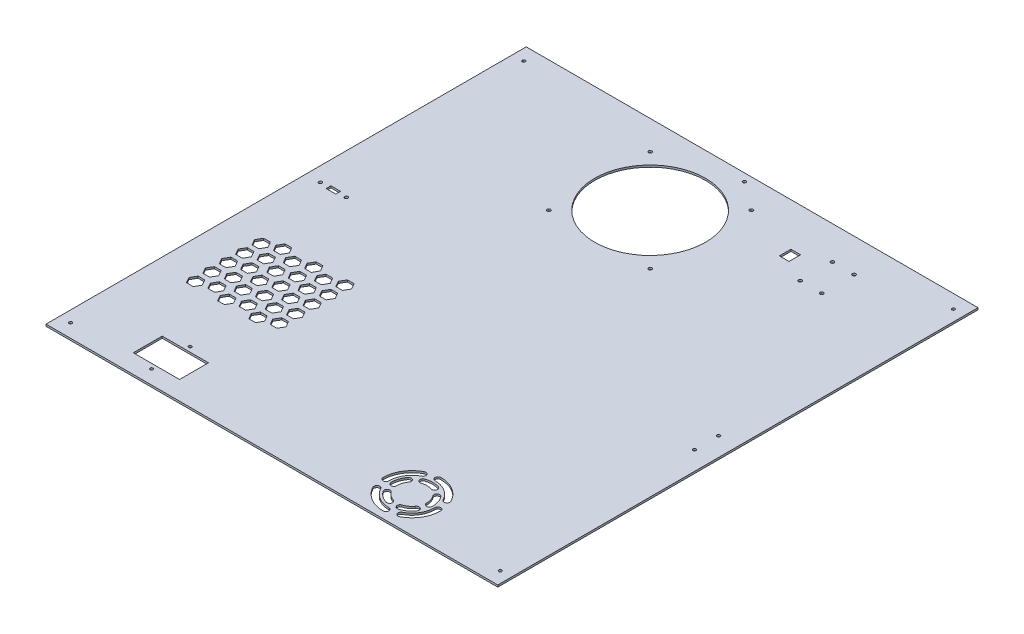
SolidWorks part; units mm, degrees
ref_plane "Alzado" through (0, 0, 0) normal (0, 0, 1) x (1, 0, 0)
ref_plane "Planta" through (0, 0, 0) normal (0, 1, 0) x (1, 0, 0)
ref_plane "Vista lateral" through (0, 0, 0) normal (1, 0, 0) x (0, 0, -1)
sketch "Croquis1" plane through (0, 0, 0) normal (0, 1, 0) x (1, 0, 0)
  line L1 (0, 0) -> (470.5, 0)
  line L2 (0, 0) -> (0, 420)
  line L3 (0, 420) -> (470.5, 420)
  line L4 (470.5, 0) -> (470.5, 420)
  dimension "D1" = 420
  dimension "D2" = 470.5
extrude "Saliente-Extruir1" add sketch "Croquis1" along normal blind 2
sketch "Croquis2" plane through (0, 2, 0) normal (0, 1, 0) x (1, 0, 0)
  line L0 (470.5, 420) -> (0, 420) construction
  line L1 (0, 420) -> (0, 0) construction
  line L2 (235.25, 420) -> (235.25, 0) construction
  line L3 (0, 0) -> (470.5, 0) construction
  line L4 (0, 210) -> (470.5, 210) construction
  line L5 (470.5, 0) -> (470.5, 420) construction
  circle A0 centre (12.5, 405) radius 1.55
  circle A1 centre (458, 405) radius 1.55
  circle A2 centre (458, 15) radius 1.55
  circle A3 centre (12.5, 15) radius 1.55
  dimension "D1" = 3.1
  dimension "D2" = 15
  dimension "D3" = 12.5
extrude "Cortar-Extruir1" cut sketch "Croquis2" against normal up to surface (2 mm away) up to face at (235.25, 0, -210)
sketch "Croquis3" plane through (0, 2, 0) normal (0, 1, 0) x (1, 0, 0)
  line L0 (470, 419.5) -> (0.5, 419.5)
  line L1 (0.5, 419.5) -> (0.5, 0.5)
  line L2 (0.5, 0.5) -> (470, 0.5)
  line L3 (470, 0.5) -> (470, 419.5)
  line L4 (0, 420) -> (0, 0)
  line L5 (0, 0) -> (470.5, 0)
  line L6 (470.5, 0) -> (470.5, 420)
  line L7 (470.5, 420) -> (0, 420)
  line L8 (0, 420) -> (0, 0)
  line L9 (0, 0) -> (470.5, 0)
  line L10 (470.5, 0) -> (470.5, 420)
  line L11 (470.5, 420) -> (0, 420)
  dimension "D1" = 0
  dimension "D2" = 0.5
extrude "Cortar-Extruir2" cut sketch "Croquis3" against normal up to surface (2 mm away) up to face at (12.5, 0, -16.55)
sketch "Croquis4" plane through (0, 2, 0) normal (0, 1, 0) x (1, 0, 0)
  line L0 (0.5, 0.5) -> (470, 0.5) construction
  line L1 (0.5, 419.5) -> (0.5, 0.5) construction
  circle A0 centre (343.5, 38) radius 27 construction
  arc A1 (343.5, 65) -> (367.4419, 50.4815) centre (343.5, 38) cw construction
  arc A2 (370.1021, 51.8683) -> (343.5, 68) centre (343.5, 38) ccw
  arc A3 (364.7817, 49.0947) -> (343.5, 62) centre (343.5, 38) ccw
  arc A4 (364.7817, 49.0947) -> (370.1021, 51.8683) centre (367.4419, 50.4815) ccw
  arc A5 (343.5, 68) -> (343.5, 62) centre (343.5, 65) ccw
  arc A6 (354.5947, 16.7183) -> (367.5, 38) centre (343.5, 38) ccw
  arc A7 (354.5947, 16.7183) -> (357.3683, 11.3979) centre (355.9815, 14.0581) ccw
  arc A8 (373.5, 38) -> (367.5, 38) centre (370.5, 38) ccw
  arc A9 (357.3683, 11.3979) -> (373.5, 38) centre (343.5, 38) ccw
  arc A10 (370.5, 38) -> (355.9815, 14.0581) centre (343.5, 38) cw construction
  arc A11 (322.2183, 26.9053) -> (343.5, 14) centre (343.5, 38) ccw
  arc A12 (322.2183, 26.9053) -> (316.8979, 24.1317) centre (319.5581, 25.5185) ccw
  arc A13 (343.5, 8) -> (343.5, 14) centre (343.5, 11) ccw
  arc A14 (316.8979, 24.1317) -> (343.5, 8) centre (343.5, 38) ccw
  arc A15 (343.5, 11) -> (319.5581, 25.5185) centre (343.5, 38) cw construction
  arc A16 (332.4053, 59.2817) -> (319.5, 38) centre (343.5, 38) ccw
  arc A17 (332.4053, 59.2817) -> (329.6317, 64.6021) centre (331.0185, 61.9419) ccw
  arc A18 (313.5, 38) -> (319.5, 38) centre (316.5, 38) ccw
  arc A19 (329.6317, 64.6021) -> (313.5, 38) centre (343.5, 38) ccw
  arc A20 (316.5, 38) -> (331.0185, 61.9419) centre (343.5, 38) cw construction
  circle A21 centre (343.5, 38) radius 18.5 construction
  arc A22 (337.5, 55.5) -> (349.5, 55.5) centre (343.5, 38) cw construction
  arc A23 (350.473, 58.3378) -> (336.527, 58.3378) centre (343.5, 38) ccw
  arc A24 (348.527, 52.6622) -> (338.473, 52.6622) centre (343.5, 38) ccw
  arc A25 (348.527, 52.6622) -> (350.473, 58.3378) centre (349.5, 55.5) ccw
  arc A26 (336.527, 58.3378) -> (338.473, 52.6622) centre (337.5, 55.5) ccw
  arc A27 (358.2894, 49.1141) -> (361.9976, 37.7015) centre (343.5, 38) cw construction
  arc A28 (364.9972, 37.653) -> (360.6877, 50.9164) centre (343.5, 38) ccw
  arc A29 (358.998, 37.7499) -> (355.8911, 47.3118) centre (343.5, 38) ccw
  arc A30 (358.998, 37.7499) -> (364.9972, 37.653) centre (361.9976, 37.7015) ccw
  arc A31 (360.6877, 50.9164) -> (355.8911, 47.3118) centre (358.2894, 49.1141) ccw
  arc A32 (358.6403, 27.3689) -> (348.9321, 20.3155) centre (343.5, 38) cw construction
  arc A33 (349.813, 17.4477) -> (361.0955, 25.645) centre (343.5, 38) ccw
  arc A34 (348.0513, 23.1832) -> (356.1852, 29.0929) centre (343.5, 38) ccw
  arc A35 (348.0513, 23.1832) -> (349.813, 17.4477) centre (348.9321, 20.3155) ccw
  arc A36 (361.0955, 25.645) -> (356.1852, 29.0929) centre (358.6403, 27.3689) ccw
  arc A37 (338.0679, 20.3155) -> (328.3597, 27.3689) centre (343.5, 38) cw construction
  arc A38 (325.9045, 25.645) -> (337.187, 17.4477) centre (343.5, 38) ccw
  arc A39 (330.8148, 29.0929) -> (338.9487, 23.1832) centre (343.5, 38) ccw
  arc A40 (330.8148, 29.0929) -> (325.9045, 25.645) centre (328.3597, 27.3689) ccw
  arc A41 (337.187, 17.4477) -> (338.9487, 23.1832) centre (338.0679, 20.3155) ccw
  arc A42 (325.0024, 37.7015) -> (328.7106, 49.1141) centre (343.5, 38) cw construction
  arc A43 (326.3123, 50.9164) -> (322.0028, 37.653) centre (343.5, 38) ccw
  arc A44 (331.1089, 47.3118) -> (328.002, 37.7499) centre (343.5, 38) ccw
  arc A45 (331.1089, 47.3118) -> (326.3123, 50.9164) centre (328.7106, 49.1141) ccw
  arc A46 (322.0028, 37.653) -> (328.002, 37.7499) centre (325.0024, 37.7015) ccw
  circle A94 centre (458, 405) radius 1.55 construction
  point P9 (357.5, 61.0868)
  point P19 (366.5868, 24)
  point P26 (329.5, 14.9132)
  point P33 (320.4132, 52)
  point P38 (343.5, 38)
  point P40 (343.5, 56.5)
  point P48 (361.0945, 43.7168)
  point P57 (354.374, 23.0332)
  point P64 (332.626, 23.0332)
  point P71 (325.9055, 43.7168)
  point P76 (343.5, 38)
  point P125 (302, 221.5)
  point P183 (302, 221.5)
  dimension "D1" = 54
  dimension "D7" = 37
  dimension "D2" = 37.5
  dimension "D3" = 343
  dimension "D4" = 28
  dimension "D5" = 6
  dimension "D8" = 12
  dimension "D9" = 6
  dimension "D6" = 4
  dimension "D10" = 5
extrude "Cortar-Extruir3" cut sketch "Croquis4" against normal up to surface (2 mm away) up to face at (12.5, 0, -406.55)
sketch "Croquis5" plane through (0, 0, 0) normal (0, -1, 0) x (1, 0, 0)
  line L0 (120, -35.5) -> (72, -35.5) construction
  line L1 (120, -50.5) -> (72, -50.5)
  line L2 (120, -50.5) -> (120, -20.5)
  line L3 (120, -20.5) -> (72, -20.5)
  line L4 (72, -50.5) -> (72, -20.5)
  line L5 (470, -0.5) -> (470, -419.5) construction
  line L6 (0.5, -0.5) -> (470, -0.5) construction
  circle A1 centre (96, -15.5) radius 1.55
  circle A2 centre (96, -55.5) radius 1.55
  dimension "D3" = 3.1
  dimension "D1" = 48
  dimension "D2" = 30
  dimension "D4" = 5
  dimension "D5" = 24
  dimension "D6" = 350
  dimension "D7" = 20
extrude "Cortar-Extruir4" cut sketch "Croquis5" against normal up to surface (2 mm away) up to face at (343.5, 2, -55.5135)
sketch "Croquis8" plane through (0, 0, 0) normal (0, -1, 0) x (1, 0, 0)
  line L1 (470, -419.5) -> (0.5, -419.5)
  line L2 (470, -419.5) -> (470, -449.5)
  line L3 (470, -449.5) -> (0.5, -449.5)
  line L4 (0.5, -419.5) -> (0.5, -449.5)
  dimension "D1" = 30
extrude "Saliente-Extruir2" add sketch "Croquis8" against normal up to surface (2 mm away) up to face at (96, 2, -57.05)
sketch "Croquis10" plane through (0, 0, 0) normal (0, -1, 0) x (1, 0, 0)
  circle A0 centre (458, -405) radius 1.75
  circle A1 centre (12.5, -405) radius 1.75
  dimension "D1" = 3.5
  dimension "D2" = 3.5
extrude "Saliente-Extruir3" add sketch "Croquis10" against normal up to surface (2 mm away) up to face at (96, 2, -57.05)
sketch "Croquis11" plane through (0, 0, -449.5) normal (0, 0, -1) x (-1, 0, 0)
  line L4 (-0.5, 2) -> (-470, 2)
  line L5 (-470, 2) -> (-470, 0)
  line L6 (-470, 0) -> (-0.5, 0)
  line L7 (-0.5, 0) -> (-0.5, 2)
  line L8 (-0.5, 2) -> (-470, 2)
  line L9 (-470, 2) -> (-470, 0)
  line L10 (-470, 0) -> (-0.5, 0)
  line L11 (-0.5, 0) -> (-0.5, 2)
  dimension "D1" = 0
extrude "Saliente-Extruir4" add sketch "Croquis11" along normal blind 50
sketch "Croquis12" plane through (0, 0, 0) normal (0, -1, 0) x (1, 0, 0)
  line L0 (470, -0.5) -> (470, -499.5) construction
  line L1 (0.5, -499.5) -> (0.5, -0.5) construction
  line L3 (470, -499.5) -> (0.5, -499.5) construction
  circle A0 centre (458, -485) radius 1.55
  circle A1 centre (12.5, -485) radius 1.55
  dimension "D1" = 3.1
  dimension "D2" = 3.1
  dimension "D3" = 12
  dimension "D4" = 12
  dimension "D5" = 14.5
  dimension "D6" = 14.5
extrude "Cortar-Extruir8" cut sketch "Croquis12" against normal up to surface (2 mm away) up to face at (96, 2, -57.05)
sketch "Croquis13" plane through (0, 0, 0) normal (0, -1, 0) x (1, 0, 0)
  line L0 (470, -0.5) -> (470, -499.5) construction
  line L1 (470, -499.5) -> (0.5, -499.5) construction
  line L3 (330, -454.5) -> (320, -454.5)
  line L4 (330, -454.5) -> (330, -442.5)
  line L5 (330, -442.5) -> (320, -442.5)
  line L6 (320, -454.5) -> (320, -442.5)
  circle A0 centre (353, -464.5) radius 1.75
  circle A1 centre (353, -431) radius 1.75
  circle A2 centre (375.5, -464.5) radius 1.75
  circle A3 centre (375.5, -431) radius 1.75
  point P16 (0, 0)
  point P17 (0, 0)
  dimension "D1" = 3.5
  dimension "D2" = 33.5
  dimension "D3" = 117
  dimension "D4" = 35
  dimension "D5" = 10
  dimension "D6" = 12
  dimension "D7" = 45
  dimension "D8" = 150
  dimension "D9" = 22.5
  dimension "D10" = 22.5
extrude "Cortar-Extruir9" cut sketch "Croquis13" against normal up to surface (2 mm away) up to face at (458, 2, -486.55)
sketch "Croquis15" plane through (0, 0, 0) normal (0, -1, 0) x (1, 0, 0)
  line L0 (470, -0.5) -> (470, -499.5) construction
  line L2 (470, -499.5) -> (0.5, -499.5) construction
  circle A0 centre (450, -249.5) radius 1.6
  circle A1 centre (450, -224.5) radius 1.6
  dimension "D1" = 3.2
  dimension "D2" = 25
  dimension "D3" = 20
  dimension "D4" = 250
extrude "Cortar-Extruir11" cut sketch "Croquis15" against normal up to surface (2 mm away) up to face at (353, 2, -432.75)
sketch "Croquis16" plane through (0, 0, 0) normal (0, -1, 0) x (1, 0, 0)
  line L4 (0.5, -0.5) -> (470, -0.5) construction
  line L5 (0.5, -499.5) -> (0.5, -0.5) construction
  line L6 (470, -0.5) -> (470, -499.5) construction
  line L7 (470, -499.5) -> (0.5, -499.5) construction
  line L8 (1, -1) -> (1, -499)
  line L9 (1, -499) -> (469.5, -499)
  line L10 (469.5, -499) -> (469.5, -1)
  line L11 (469.5, -1) -> (1, -1)
  line L12 (1, -1) -> (1, -499)
  line L13 (1, -499) -> (469.5, -499)
  line L14 (469.5, -499) -> (469.5, -1)
  line L15 (469.5, -1) -> (1, -1)
  line L16 (0.5, -0.5) -> (470, -0.5)
  line L17 (0.5, -499.5) -> (0.5, -0.5)
  line L18 (470, -0.5) -> (470, -499.5)
  line L19 (470, -499.5) -> (0.5, -499.5)
  dimension "D1" = 0.5
extrude "Cortar-Extruir12" cut sketch "Croquis16" against normal up to surface (2 mm away) up to face at (450, 2, -251.1)
sketch "Croquis17" plane through (0, 2, 0) normal (0, 1, 0) x (1, 0, 0)
  line L0 (469.5, 499) -> (1, 499) construction
  line L1 (1, 499) -> (1, 1) construction
  circle A0 centre (235.25, 491) radius 1.6
  dimension "D1" = 3.2
  dimension "D2" = 8
  dimension "D3" = 234.25
extrude "Cortar-Extruir13" cut sketch "Croquis17" against normal up to surface (2 mm away) up to face at (12.5, 0, -16.55)
sketch "Croquis18" plane through (0, 0, 0) normal (0, -1, 0) x (1, 0, 0)
  line L0 (34.5, -270.5) -> (16, -270.5) construction
  line L1 (34.5, -273) -> (24.5, -273)
  line L2 (34.5, -273) -> (34.5, -268)
  line L3 (34.5, -268) -> (24.5, -268)
  line L4 (24.5, -273) -> (24.5, -268)
  line L5 (34.5, -270.5) -> (43, -270.5) construction
  line L6 (29.5, -273) -> (29.5, -268) construction
  line L7 (1, -1) -> (1, -499) construction
  line L9 (72, -50.5) -> (120, -50.5) construction
  circle A0 centre (16, -270.5) radius 1.65
  circle A1 centre (43, -270.5) radius 1.65
  dimension "D3" = 3.3
  dimension "D4" = 3.3
  dimension "D1" = 10
  dimension "D2" = 5
  dimension "D5" = 27
  dimension "D6" = 13.5
  dimension "D7" = 15
  dimension "D8" = 220
extrude "Cortar-Extruir14" cut sketch "Croquis18" against normal up to surface (2 mm away) up to face at (235.25, 2, -489.4)
sketch "Croquis19" plane through (0, 0, 0) normal (0, -1, 0) x (1, 0, 0)
  line L0 (1, -1) -> (1, -499) construction
  line L1 (114.0718, -191) -> (117.5359, -197)
  line L2 (117.5359, -197) -> (124.4641, -197)
  line L3 (124.4641, -197) -> (127.9282, -191)
  line L4 (127.9282, -191) -> (124.4641, -185)
  line L5 (124.4641, -185) -> (117.5359, -185)
  line L6 (117.5359, -185) -> (114.0718, -191)
  line L7 (469.5, -1) -> (1, -1) construction
  line L176 (114.0718, -174) -> (117.5359, -180)
  line L177 (97.906, -185) -> (101.3701, -191)
  line L178 (101.3701, -191) -> (108.2983, -191)
  line L179 (108.2983, -191) -> (111.7624, -185)
  line L180 (111.7624, -185) -> (108.2983, -179)
  line L181 (108.2983, -179) -> (101.3701, -179)
  line L182 (101.3701, -179) -> (97.906, -185)
  line L183 (117.5359, -180) -> (124.4641, -180)
  line L184 (124.4641, -180) -> (127.9282, -174)
  line L185 (127.9282, -174) -> (124.4641, -168)
  line L186 (124.4641, -168) -> (117.5359, -168)
  line L187 (117.5359, -168) -> (114.0718, -174)
  line L188 (97.906, -168) -> (101.3701, -174)
  line L189 (101.3701, -174) -> (108.2983, -174)
  line L190 (108.2983, -174) -> (111.7624, -168)
  line L191 (111.7624, -168) -> (108.2983, -162)
  line L192 (108.2983, -162) -> (101.3701, -162)
  line L193 (101.3701, -162) -> (97.906, -168)
  line L194 (114.0718, -157) -> (117.5359, -163)
  line L195 (117.5359, -163) -> (124.4641, -163)
  line L196 (124.4641, -163) -> (127.9282, -157)
  line L197 (127.9282, -157) -> (124.4641, -151)
  line L198 (124.4641, -151) -> (117.5359, -151)
  line L199 (117.5359, -151) -> (114.0718, -157)
  line L200 (97.906, -151) -> (101.3701, -157)
  line L201 (101.3701, -157) -> (108.2983, -157)
  line L202 (108.2983, -157) -> (111.7624, -151)
  line L203 (111.7624, -151) -> (108.2983, -145)
  line L204 (108.2983, -145) -> (101.3701, -145)
  line L205 (101.3701, -145) -> (97.906, -151)
  line L206 (114.0718, -140) -> (117.5359, -146)
  line L207 (117.5359, -146) -> (124.4641, -146)
  line L208 (124.4641, -146) -> (127.9282, -140)
  line L209 (127.9282, -140) -> (124.4641, -134)
  line L210 (124.4641, -134) -> (117.5359, -134)
  line L211 (117.5359, -134) -> (114.0718, -140)
  line L212 (97.906, -134) -> (101.3701, -140)
  line L213 (101.3701, -140) -> (108.2983, -140)
  line L214 (108.2983, -140) -> (111.7624, -134)
  line L215 (111.7624, -134) -> (108.2983, -128)
  line L216 (108.2983, -128) -> (101.3701, -128)
  line L217 (101.3701, -128) -> (97.906, -134)
  line L218 (114.0718, -123) -> (117.5359, -129)
  line L219 (117.5359, -129) -> (124.4641, -129)
  line L220 (124.4641, -129) -> (127.9282, -123)
  line L221 (127.9282, -123) -> (124.4641, -117)
  line L222 (124.4641, -117) -> (117.5359, -117)
  line L223 (117.5359, -117) -> (114.0718, -123)
  line L224 (97.906, -117) -> (101.3701, -123)
  line L225 (101.3701, -123) -> (108.2983, -123)
  line L226 (108.2983, -123) -> (111.7624, -117)
  line L227 (111.7624, -117) -> (108.2983, -111)
  line L228 (108.2983, -111) -> (101.3701, -111)
  line L229 (101.3701, -111) -> (97.906, -117)
  line L230 (81.7402, -191) -> (85.2043, -197)
  line L231 (85.2043, -197) -> (92.1325, -197)
  line L232 (92.1325, -197) -> (95.5966, -191)
  line L233 (95.5966, -191) -> (92.1325, -185)
  line L234 (92.1325, -185) -> (85.2043, -185)
  line L235 (85.2043, -185) -> (81.7402, -191)
  line L236 (81.7402, -174) -> (85.2043, -180)
  line L237 (65.5744, -185) -> (69.0385, -191)
  line L238 (69.0385, -191) -> (75.9667, -191)
  line L239 (75.9667, -191) -> (79.4308, -185)
  line L240 (79.4308, -185) -> (75.9667, -179)
  line L241 (75.9667, -179) -> (69.0385, -179)
  line L242 (69.0385, -179) -> (65.5744, -185)
  line L243 (85.2043, -180) -> (92.1325, -180)
  line L244 (92.1325, -180) -> (95.5966, -174)
  line L245 (95.5966, -174) -> (92.1325, -168)
  line L246 (92.1325, -168) -> (85.2043, -168)
  line L247 (85.2043, -168) -> (81.7402, -174)
  line L248 (65.5744, -168) -> (69.0385, -174)
  line L249 (69.0385, -174) -> (75.9667, -174)
  line L250 (75.9667, -174) -> (79.4308, -168)
  line L251 (79.4308, -168) -> (75.9667, -162)
  line L252 (75.9667, -162) -> (69.0385, -162)
  line L253 (69.0385, -162) -> (65.5744, -168)
  line L254 (81.7402, -157) -> (85.2043, -163)
  line L255 (85.2043, -163) -> (92.1325, -163)
  line L256 (92.1325, -163) -> (95.5966, -157)
  line L257 (95.5966, -157) -> (92.1325, -151)
  line L258 (92.1325, -151) -> (85.2043, -151)
  line L259 (85.2043, -151) -> (81.7402, -157)
  line L260 (65.5744, -151) -> (69.0385, -157)
  line L261 (69.0385, -157) -> (75.9667, -157)
  line L262 (75.9667, -157) -> (79.4308, -151)
  line L263 (79.4308, -151) -> (75.9667, -145)
  line L264 (75.9667, -145) -> (69.0385, -145)
  line L265 (69.0385, -145) -> (65.5744, -151)
  line L266 (81.7402, -140) -> (85.2043, -146)
  line L267 (85.2043, -146) -> (92.1325, -146)
  line L268 (92.1325, -146) -> (95.5966, -140)
  line L269 (95.5966, -140) -> (92.1325, -134)
  line L270 (92.1325, -134) -> (85.2043, -134)
  line L271 (85.2043, -134) -> (81.7402, -140)
  line L272 (65.5744, -134) -> (69.0385, -140)
  line L273 (69.0385, -140) -> (75.9667, -140)
  line L274 (75.9667, -140) -> (79.4308, -134)
  line L275 (79.4308, -134) -> (75.9667, -128)
  line L276 (75.9667, -128) -> (69.0385, -128)
  line L277 (69.0385, -128) -> (65.5744, -134)
  line L278 (81.7402, -123) -> (85.2043, -129)
  line L279 (85.2043, -129) -> (92.1325, -129)
  line L280 (92.1325, -129) -> (95.5966, -123)
  line L281 (95.5966, -123) -> (92.1325, -117)
  line L282 (92.1325, -117) -> (85.2043, -117)
  line L283 (85.2043, -117) -> (81.7402, -123)
  line L284 (65.5744, -117) -> (69.0385, -123)
  line L285 (69.0385, -123) -> (75.9667, -123)
  line L286 (75.9667, -123) -> (79.4308, -117)
  line L287 (79.4308, -117) -> (75.9667, -111)
  line L288 (75.9667, -111) -> (69.0385, -111)
  line L289 (69.0385, -111) -> (65.5744, -117)
  line L290 (49.4086, -191) -> (52.8727, -197)
  line L291 (52.8727, -197) -> (59.8009, -197)
  line L292 (59.8009, -197) -> (63.265, -191)
  line L293 (63.265, -191) -> (59.8009, -185)
  line L294 (59.8009, -185) -> (52.8727, -185)
  line L295 (52.8727, -185) -> (49.4086, -191)
  line L296 (49.4086, -174) -> (52.8727, -180)
  line L297 (33.2428, -185) -> (36.7069, -191)
  line L298 (36.7069, -191) -> (43.6351, -191)
  line L299 (43.6351, -191) -> (47.0992, -185)
  line L300 (47.0992, -185) -> (43.6351, -179)
  line L301 (43.6351, -179) -> (36.7069, -179)
  line L302 (36.7069, -179) -> (33.2428, -185)
  line L303 (52.8727, -180) -> (59.8009, -180)
  line L304 (59.8009, -180) -> (63.265, -174)
  line L305 (63.265, -174) -> (59.8009, -168)
  line L306 (59.8009, -168) -> (52.8727, -168)
  line L307 (52.8727, -168) -> (49.4086, -174)
  line L308 (33.2428, -168) -> (36.7069, -174)
  line L309 (36.7069, -174) -> (43.6351, -174)
  line L310 (43.6351, -174) -> (47.0992, -168)
  line L311 (47.0992, -168) -> (43.6351, -162)
  line L312 (43.6351, -162) -> (36.7069, -162)
  line L313 (36.7069, -162) -> (33.2428, -168)
  line L314 (49.4086, -157) -> (52.8727, -163)
  line L315 (52.8727, -163) -> (59.8009, -163)
  line L316 (59.8009, -163) -> (63.265, -157)
  line L317 (63.265, -157) -> (59.8009, -151)
  line L318 (59.8009, -151) -> (52.8727, -151)
  line L319 (52.8727, -151) -> (49.4086, -157)
  line L320 (33.2428, -151) -> (36.7069, -157)
  line L321 (36.7069, -157) -> (43.6351, -157)
  line L322 (43.6351, -157) -> (47.0992, -151)
  line L323 (47.0992, -151) -> (43.6351, -145)
  line L324 (43.6351, -145) -> (36.7069, -145)
  line L325 (36.7069, -145) -> (33.2428, -151)
  line L326 (49.4086, -140) -> (52.8727, -146)
  line L327 (52.8727, -146) -> (59.8009, -146)
  line L328 (59.8009, -146) -> (63.265, -140)
  line L329 (63.265, -140) -> (59.8009, -134)
  line L330 (59.8009, -134) -> (52.8727, -134)
  line L331 (52.8727, -134) -> (49.4086, -140)
  line L332 (33.2428, -134) -> (36.7069, -140)
  line L333 (36.7069, -140) -> (43.6351, -140)
  line L334 (43.6351, -140) -> (47.0992, -134)
  line L335 (47.0992, -134) -> (43.6351, -128)
  line L336 (43.6351, -128) -> (36.7069, -128)
  line L337 (36.7069, -128) -> (33.2428, -134)
  line L338 (49.4086, -123) -> (52.8727, -129)
  line L339 (52.8727, -129) -> (59.8009, -129)
  line L340 (59.8009, -129) -> (63.265, -123)
  line L341 (63.265, -123) -> (59.8009, -117)
  line L342 (59.8009, -117) -> (52.8727, -117)
  line L343 (52.8727, -117) -> (49.4086, -123)
  line L344 (33.2428, -117) -> (36.7069, -123)
  line L345 (36.7069, -123) -> (43.6351, -123)
  line L346 (43.6351, -123) -> (47.0992, -117)
  line L347 (47.0992, -117) -> (43.6351, -111)
  line L348 (43.6351, -111) -> (36.7069, -111)
  line L349 (36.7069, -111) -> (33.2428, -117)
  circle A0 centre (121, -191) radius 6 construction
  circle A1 centre (104.8342, -185) radius 6 construction
  dimension "D1" = 12
  dimension "D2" = 190
  dimension "D3" = 120
  dimension "D6" = 5
  dimension "D7" = 5
  dimension "D4" = 5
  dimension "D5" = 12
  dimension "D9" = 5
  dimension "D8" = 3
extrude "Cortar-Extruir15" cut sketch "Croquis19" against normal up to surface (2 mm away) up to face at (43, 2, -272.15)
sketch "Croquis20" plane through (0, 0, 0) normal (0, -1, 0) x (1, 0, 0)
  line L0 (1, -499) -> (469.5, -499) construction
  line L1 (264.5, -469) -> (159.5, -469) construction
  line L2 (264.5, -469) -> (264.5, -364) construction
  line L3 (264.5, -364) -> (159.5, -364) construction
  line L4 (159.5, -469) -> (159.5, -364) construction
  line L5 (469.5, -499) -> (469.5, -1) construction
  line L6 (159.5, -469) -> (264.5, -364) construction
  circle A0 centre (264.5, -469) radius 1.75
  circle A1 centre (159.5, -469) radius 1.75
  circle A2 centre (159.5, -364) radius 1.75
  circle A3 centre (264.5, -364) radius 1.75
  circle A4 centre (212, -416.5) radius 57.5
  dimension "D5" = 3.5
  dimension "D6" = 115
  dimension "D1" = 105
  dimension "D2" = 105
  dimension "D3" = 30
  dimension "D4" = 205
extrude "Cortar-Extruir16" cut sketch "Croquis20" against normal up to surface (2 mm away) up to face at (72.5026, 2, -168)
